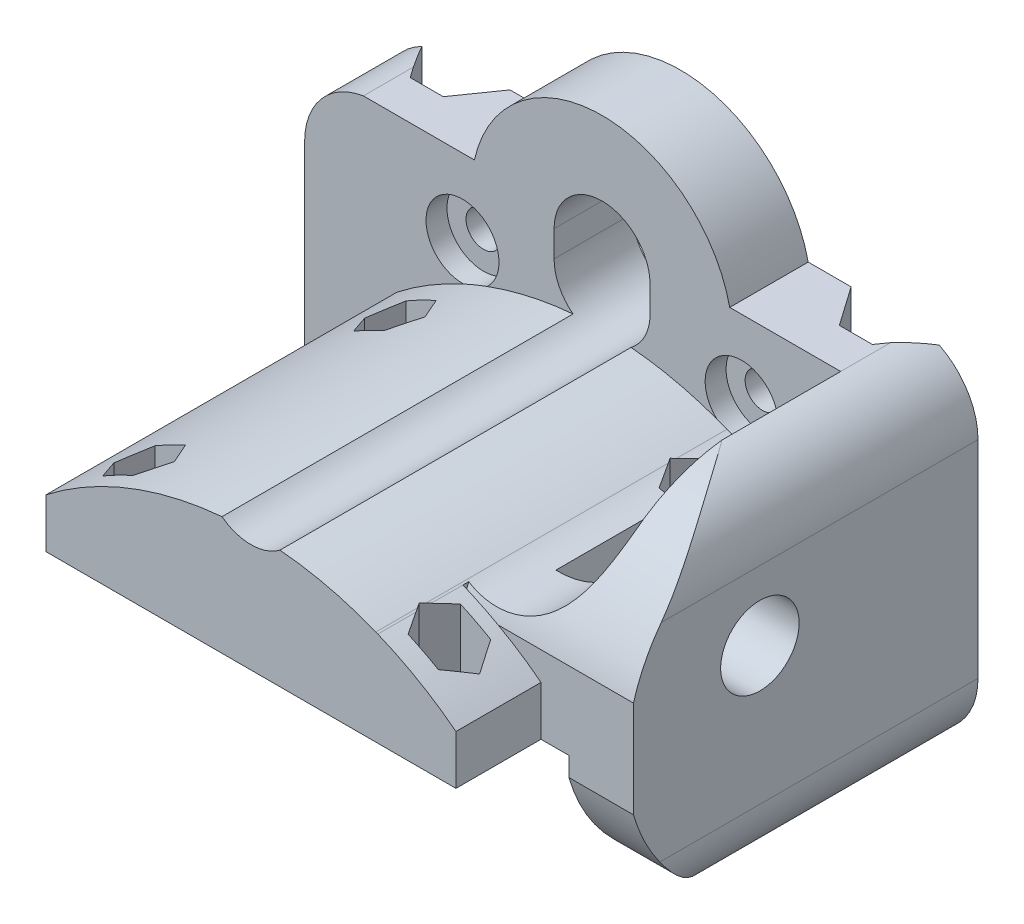
SolidWorks part; units mm, degrees
note: The reader was unsure of these and kept them because the rebuilt part matched: shared geometry of "Sketch9<7>".
ref_plane "Front Plane" through (0, 0, 0) normal (0, 0, 1) x (1, 0, 0)
ref_plane "Top Plane" through (0, 0, 0) normal (0, 1, 0) x (1, 0, 0)
ref_plane "Right Plane" through (0, 0, 0) normal (1, 0, 0) x (0, 0, -1)
sketch "Sketch1" plane through (0, 0, 0) normal (0, 0, 1) x (1, 0, 0)
  line L0 (34.1, -14.8502) -> (34.1, 8.8502)
  line L1 (-34.1, -14.8502) -> (-34.1, 8.8502)
  line L2 (-14.6356, 16.75) -> (-27.3591, 16.75)
  line L3 (14.6356, 16.75) -> (27.3591, 16.75)
  line L4 (-11.5, -22.75) -> (-27.5591, -22.75)
  line L5 (11.5, -22.75) -> (27.3591, -22.75)
  line L6 (7.5, -18.75) -> (7.5, -16.0002)
  line L7 (-7.5, -16.0002) -> (-7.5, -18.75)
  line L8 (0, -8.5446) -> (0, 28.5) construction
  line L9 (34.1, 0) -> (-34.1, 0) construction
  arc A0 (27.3591, -22.75) -> (34.1, -14.8502) centre (26.1005, -14.8502) ccw
  arc A1 (7.5, -18.75) -> (11.5, -22.75) centre (11.5, -18.75) ccw
  arc A2 (34.1, 8.8502) -> (27.3591, 16.75) centre (26.1005, 8.8502) ccw
  arc A3 (-34.1, 8.8502) -> (-27.3591, 16.75) centre (-26.1005, 8.8502) cw
  arc A4 (-27.3591, -22.75) -> (-34.1, -14.8502) centre (-26.1005, -14.8502) cw
  arc A5 (-7.5, -18.75) -> (-11.5, -22.75) centre (-11.5, -18.75) cw
  arc A6 (14.6356, 16.75) -> (-14.6356, 16.75) centre (0, 13.5101) ccw
  arc A7 (7.5, -16.0892) -> (-7.5, -16.0892) centre (0, -16.0447) ccw
  circle A8 centre (16.0001, 8) radius 2
  circle A9 centre (16.0001, -16.5) radius 2
  circle A10 centre (-16.0001, -16.5) radius 2
  circle A11 centre (-16.0001, 8) radius 2
  dimension "D1" = 4
  dimension "D2" = 4.0001
  dimension "D3" = 7.9995
  dimension "D4" = 4.0001
  dimension "D5" = 7.5
  dimension "D6" = 14.9899
  dimension "D7" = 7.5001
  dimension "D8" = 14.6356
  dimension "D9" = 16.0001
  dimension "D10" = 26.1005
  dimension "D11" = 27.3591
  dimension "D12" = 8
  dimension "D13" = 8.8502
  dimension "D14" = 14.8502
  dimension "D15" = 16.0002
  dimension "D18" = 27.5591
  dimension "D25" = 16.5
extrude "Boss-Extrude1" add sketch "Sketch1" along normal mid plane 9 contours A7 L6 A1 L5 A0 L0 A2 L3 A6 L2 A3 L1 A4 L4 A5 L7 A10 A9 A8 A11
sketch "Sketch3" plane through (0, 0, 4.5) normal (0, 0, 1) x (1, 0, 0)
  line L0 (0, 28.5) -> (0, -8.5446) construction
  line L1 (-5.5, 14.5) -> (-5.5, 11.5) construction
  line L6 (-5.5, 11.5) -> (-5.5, 14.5)
  line L7 (5.5, 11.5) -> (5.5, 14.5)
  line L14 (-34.1, -4.25) -> (34.1, -4.25) construction
  line L15 (-34.1, -14.8502) -> (-34.1, 8.8502) construction
  line L26 (34.1, -14.8502) -> (34.1, 8.8502) construction
  line L27 (11.5, -22.75) -> (27.3591, -22.75) construction
  arc A0 (14.6356, 16.75) -> (-14.6356, 16.75) centre (0, 13.5101) ccw construction
  circle A1 centre (-16.0001, 8) radius 4.1817
  arc A2 (7.5, -16.0892) -> (-7.5, -16.0892) centre (0, -16.0447) ccw construction
  arc A3 (-5.5, 14.5) -> (5.5, 14.5) centre (0, 14.5) cw
  arc A4 (-5.5, 11.5) -> (5.5, 11.5) centre (0, 11.5) ccw
  circle A5 centre (16.0001, 8) radius 4.1817
  circle A6 centre (16.0001, -16.5) radius 4.1817
  circle A7 centre (-16.0001, -16.5) radius 4.1817
  point P28 (0, 0)
  dimension "D1" = 32.8591
  dimension "D2" = 6.25
  dimension "D3" = 5.5
  dimension "D5" = 5.5
  dimension "D8" = 8.3635
  dimension "D4" = 14.5
  dimension "D6" = 3
  dimension "D7" = 5.5
  dimension "D10" = 37.25
sketch "Sketch4" plane through (0, 0, 4.5) normal (0, 0, 1) x (1, 0, 0)
  line L0 (5.5, 11.5) -> (5.5, 14.5) construction
  line L1 (-5.5, 11.5) -> (-5.5, 14.5) construction
  line L2 (5.5, 11.5) -> (5.5, 14.5)
  line L3 (-5.5, 11.5) -> (-5.5, 14.5)
  arc A0 (5.5, 14.5) -> (-5.5, 14.5) centre (0, 14.5) ccw construction
  arc A1 (-5.5, 11.5) -> (5.5, 11.5) centre (0, 11.5) ccw construction
  arc A2 (5.5, 14.5) -> (-5.5, 14.5) centre (0, 14.5) ccw
  arc A3 (-5.5, 11.5) -> (5.5, 11.5) centre (0, 11.5) ccw
extrude "Cut-Extrude2" cut sketch "Sketch4" against normal through all
sketch "Sketch6" plane through (0, 0, 4.5) normal (0, 0, 1) x (1, 0, 0)
  line L1 (23.5, -6.45) -> (-23.5, -6.45)
  line L2 (-23.5, -0.8) -> (23.5, -0.8)
  line L3 (-23.5, -0.8) -> (23.5, -0.8)
  line L4 (0, -8.5446) -> (0, -0.8) construction
  line L5 (-23.5, -0.8) -> (-23.5, -6.45)
  line L6 (-23.5, -6.45) -> (23.5, -6.45)
  line L7 (23.5, -0.8) -> (23.5, -6.45)
  arc A0 (3.324, 7.1181) -> (23.5, -0.8) centre (0, -31.0158) cw
  arc A2 (-5.5, 11.5) -> (5.5, 11.5) centre (0, 11.5) ccw construction
  arc A3 (-3.324, 7.1181) -> (3.324, 7.1181) centre (0, 11.5) ccw
  arc A4 (7.5, -16.0892) -> (-7.5, -16.0892) centre (0, -16.0447) ccw construction
  arc A6 (-23.5, -0.8) -> (-3.324, 7.1181) centre (0, -31.0158) cw
  point P4 (0, -6.45)
  arc M30 (5.5, 11.5) -> (-5.5, 11.5) centre (0, 11.5) cw
  dimension "D4" = 38.2785
  dimension "D1" = 47
  dimension "D2" = 0.8
  dimension "D3" = 5.65
extrude "Boss-Extrude2" add sketch "Sketch6" along normal blind 40.25 contours L4 L1 L7 L3 | L6 L4 L2 L5 | A6 L2 L3 A0 M30
sketch "Sketch9" plane through (0, 0, 0) normal (0, 1, 0) x (1, 0, 0)
  line L0 (-23.5, -44.75) -> (-3.324, -44.75) construction
  line L1 (-19.2321, -36.5) -> (-20.9641, -39.5)
  line L2 (-20.9641, -39.5) -> (-19.2321, -42.5)
  line L3 (-19.2321, -42.5) -> (-15.7679, -42.5)
  line L4 (-15.7679, -42.5) -> (-14.0359, -39.5)
  line L5 (-14.0359, -39.5) -> (-15.7679, -36.5)
  line L6 (-15.7679, -36.5) -> (-19.2321, -36.5)
  line L9 (0, 4.5) -> (0, -44.75) construction
  line L10 (14.6356, 4.5) -> (-14.6356, 4.5) construction
  line L11 (-3.324, -44.75) -> (3.324, -44.75) construction
  line L12 (14.0359, -39.5) -> (15.7679, -36.5)
  line L13 (15.7679, -42.5) -> (14.0359, -39.5)
  line L14 (19.2321, -42.5) -> (15.7679, -42.5)
  line L15 (20.9641, -39.5) -> (19.2321, -42.5)
  line L16 (19.2321, -36.5) -> (20.9641, -39.5)
  line L17 (15.7679, -36.5) -> (19.2321, -36.5)
  line L18 (22.7061, 0) -> (19.5551, 4.5)
  line L19 (-29.647, 4.5) -> (-26.4961, 0)
  line L20 (26.4961, 0) -> (22.7061, 0)
  line L21 (-26.4961, 0) -> (-22.7061, 0)
  line L22 (-22.7061, 0) -> (-19.5551, 4.5)
  line L23 (29.647, 4.5) -> (26.4961, 0)
  line L24 (19.5551, 4.5) -> (29.647, 4.5)
  line L25 (-23.5, -25.1222) -> (23.5, -25.1222) construction
  line L26 (23.5, -44.75) -> (23.5, -4.5) construction
  line L27 (14.0359, -10.7444) -> (15.7679, -13.7444)
  line L28 (15.7679, -7.7444) -> (14.0359, -10.7444)
  line L29 (19.2321, -7.7444) -> (15.7679, -7.7444)
  line L30 (20.9641, -10.7444) -> (19.2321, -7.7444)
  line L31 (-23.5, -44.75) -> (-23.5, -4.5) construction
  line L32 (19.2321, -13.7444) -> (20.9641, -10.7444)
  line L34 (15.7679, -13.7444) -> (19.2321, -13.7444)
  line L35 (-14.0359, -10.7444) -> (-15.7679, -13.7444)
  line L36 (-27.3591, 4.5) -> (-34.1, 4.5) construction
  line L38 (-19.5551, 4.5) -> (-29.647, 4.5)
  line L39 (-15.7679, -7.7444) -> (-14.0359, -10.7444)
  line L40 (-19.2321, -7.7444) -> (-15.7679, -7.7444)
  line L41 (-20.9641, -10.7444) -> (-19.2321, -7.7444)
  line L42 (-19.2321, -13.7444) -> (-20.9641, -10.7444)
  line L43 (-15.7679, -13.7444) -> (-19.2321, -13.7444)
  circle A0 centre (17.5, -10.7444) radius 1.8
  circle A1 centre (-17.5, -39.5) radius 3 construction
  circle A2 centre (-17.5, -39.5) radius 1.8
  circle A3 centre (17.5, -39.5) radius 1.8
  circle A4 centre (-17.5, -10.7444) radius 1.8
  point P38 (17.5, -10.7444)
  point P53 (-17.5, -10.7444)
  dimension "D4" = 6
  dimension "D5" = 125
  dimension "D7" = 3.6
  dimension "D1" = 125
  dimension "D2" = 6
  dimension "D3" = 5.25
  dimension "D6" = 4.453
  dimension "D8" = 3.79
  dimension "D9" = 14.3778
sketch "Sketch10" plane through (0, 0, 0) normal (1, 0, 0) x (0, 0, -1)
  circle A0 centre (-3.55, -1.87) radius 1.25
  circle A1 centre (-3.55, -11.33) radius 1.25
  point P0 (0, 0)
  dimension "D1" = 2.5
  dimension "D2" = 2.5
  dimension "D3" = 3.55
  dimension "D4" = 1.87
  dimension "D5" = 11.33
extrude "Cut-Extrude3" cut sketch "Sketch3" against normal blind 2.4
ref_plane "Plane1" through (-34.1, 0, 0) normal (-1, 0, 0) x (0, 0, 1)
ref_plane "Plane2" through (0, 0, 4.5) normal (0, 0, 1) x (1, 0, 0)
sketch "Sketch15" plane through (0, 0, 4.5) normal (0, 0, 1) x (1, 0, 0)
  line L0 (14.3143, 16.75) -> (14.3143, -22.75)
  line L1 (14.6356, 16.75) -> (27.3591, 16.75) construction
  line L2 (11.5, -22.75) -> (27.3591, -22.75) construction
  line L3 (34.1, -14.8502) -> (34.1, 8.8502) construction
  line L4 (34.1, -14.8502) -> (34.1, 8.8502)
  line L5 (14.3143, -22.75) -> (27.3591, -22.75)
  line L6 (14.3143, 16.75) -> (27.3591, 16.75)
  arc A0 (34.1, 8.8502) -> (27.3591, 16.75) centre (26.1005, 8.8502) ccw construction
  arc A1 (27.3591, -22.75) -> (34.1, -14.8502) centre (26.1005, -14.8502) ccw construction
  arc A2 (34.1, 8.8502) -> (27.3591, 16.75) centre (26.1005, 8.8502) ccw
  arc A3 (27.3591, -22.75) -> (34.1, -14.8502) centre (26.1005, -14.8502) ccw
  dimension "D1" = 19.7857
extrude "Boss-Extrude3" add sketch "Sketch15" along normal blind 30.5
sketch "Sketch17" plane through (0, 0, 0) normal (1, 0, 0) x (0, 0, -1)
  line L0 (-35, -8.6461) -> (-35, 2.4461)
  line L1 (-38.1156, 25) -> (-38.1156, -25)
  line L2 (0, 0) -> (-38.1156, 0) construction
  line L8 (-18.1156, 16.75) -> (-18.1156, 25)
  line L12 (-18.1156, 25) -> (-38.1156, 25)
  line L15 (-38.1156, -25) -> (-19.4504, -25)
  line L16 (-19.4504, -25) -> (-19.4504, -22.75)
  arc A0 (-19.4504, -22.75) -> (-35, -8.6461) centre (-15.8631, -3.1713) cw
  arc A1 (-35, 2.4461) -> (-18.1156, 16.75) centre (-15.8232, -3.0731) cw
  point P8 (0, 0)
  dimension "D1" = 19.9046
  dimension "D2" = 19.9552
  dimension "D3" = 50
  dimension "D4" = 15.8232
  dimension "D5" = 15.8631
  dimension "D6" = 18.1156
  dimension "D7" = 19.4504
  dimension "D8" = 35
  dimension "D9" = 2.4461
  dimension "D10" = 3.1713
  dimension "D11" = 20
sketch "Sketch18" plane through (0, 0, 0) normal (0, 0, 1) x (1, 0, 0)
  line L0 (26.6868, 12.5458) -> (26.6868, 18.5458)
  line L1 (26.7, -25.0473) -> (26.7, -6.35)
  line L3 (23.5, -6.45) -> (-23.5, -6.45) construction
  line L4 (26.7, -6.45) -> (14.3143, -6.45)
  line L10 (13.9387, 4.6347) -> (13.9387, 18.5458)
  line L11 (13.9387, 18.5458) -> (26.6868, 18.5458)
  line L12 (14.3143, -6.45) -> (14.3143, -25.0473)
  line L13 (14.3143, -25.0473) -> (14.2319, -25.0492)
  line L14 (26.7, -25.0473) -> (14.3143, -25.0473)
  arc A0 (26.6868, 12.5458) -> (13.9387, 4.6347) centre (17.3234, 13.4072) cw
  arc A1 (23.5, -0.8) -> (3.324, 7.1181) centre (0, -31.0158) ccw construction
  point P2 (0, 0)
  dimension "D1" = 9.4029
  dimension "D2" = 13.9387
  dimension "D3" = 14.2319
  dimension "D4" = 14.3143
  dimension "D5" = 17.3234
  dimension "D6" = 26.6868
  dimension "D7" = 26.7
  dimension "D8" = 18.5458
  dimension "D9" = 6.35
  dimension "D10" = 25.0473
  dimension "D11" = 25.0492
ref_plane "Plane3" through (0, 0, 4.5) normal (0, 0, 1) x (1, 0, 0)
ref_plane "Plane4" through (34.1, 0, 0) normal (1, 0, 0) x (0, 0, -1)
sketch "Sketch21" plane through (0, 0, 4.5) normal (0, 0, 1) x (1, 0, 0)
  line L0 (14.3143, -25.0473) -> (14.2319, -25.0492) construction
  line L1 (26.7, -6.45) -> (14.3143, -6.45) construction
  line L2 (14.3143, -6.45) -> (14.3143, -25.0473) construction
  line L3 (26.7, -25.0473) -> (26.7, -6.35) construction
  line L4 (26.7, -25.0473) -> (14.3143, -25.0473) construction
  line L5 (14.3143, 16.75) -> (27.3591, 16.75)
  line L8 (14.3143, -25.0473) -> (14.2319, -25.0492)
  line L9 (26.7, -6.45) -> (14.3143, -6.45)
  line L10 (14.3143, -6.45) -> (14.3143, -25.0473)
  line L11 (26.7, -25.0473) -> (26.7, -6.35)
  line L12 (26.7, -25.0473) -> (14.3143, -25.0473)
  line L13 (27.3591, 12.5796) -> (27.3591, 16.75)
  line L15 (14.3143, 16.75) -> (14.3143, 4.4855) construction
  line L16 (27.3591, 16.75) -> (14.3143, 16.75) construction
  line L17 (14.3143, 16.75) -> (14.3143, 4.4855)
  line L18 (27.3591, 16.75) -> (14.3143, 16.75)
  arc A1 (27.3591, 12.5796) -> (14.3143, 4.4855) centre (17.9734, 13.1473) cw
  point P8 (0, 0)
  point P11 (27.3591, 16.75)
  dimension "D1" = 9.4029
  dimension "D3" = 17.9734
  dimension "D4" = 16.75
extrude "Cut-Extrude16" cut sketch "Sketch21" along normal through all contours L12 L11 L9 L10 | A1 L13 L5 L17
sketch "Sketch22" plane through (34.1, 0, 0) normal (1, 0, 0) x (0, 0, -1)
  line L0 (-35, 2.4461) -> (-35, 18.4461)
  line L1 (-35, 16.75) -> (-4.5, 16.75) construction
  line L2 (-19.4504, -22.75) -> (-19.4504, -24.6461)
  line L3 (-35, -24.6461) -> (-35, -8.6461)
  line L4 (-19.4504, -24.6461) -> (-35, -24.6461)
  line L6 (-38.1156, -25) -> (-19.4504, -25)
  line L7 (-38.1156, 25) -> (-38.1156, -25)
  line L8 (-18.1156, 25) -> (-38.1156, 25)
  line L9 (-18.1156, 16.75) -> (-18.1156, 25)
  line L10 (-35, -8.6461) -> (-35, 2.4461)
  line L11 (-19.4504, -25) -> (-19.4504, -22.75)
  line L20 (-18.1154, 16.75) -> (-18.1154, 18.4461)
  line L21 (-18.1154, 18.4461) -> (-35, 18.4461)
  arc A2 (-18.1156, 16.75) -> (-35, 2.4461) centre (-15.8232, -3.0731) ccw
  arc A3 (-35, -8.6461) -> (-19.4504, -22.75) centre (-15.8631, -3.1713) ccw
  arc A4 (-18.1154, 16.75) -> (-35, 2.4461) centre (-15.8232, -3.0731) ccw
  arc A5 (-35, -8.6461) -> (-19.4504, -22.75) centre (-15.8631, -3.1713) ccw
  dimension "D2" = 16
  dimension "D3" = 16
  dimension "D1" = 0
extrude "Cut-Extrude20" cut sketch "Sketch22" against normal up to vertex (19.5559 mm away)
sketch "Sketch24" plane through (0, 0, 0) normal (0, 1, 0) x (1, 0, 0)
  line L0 (17.75, -16.1355) -> (19.6355, -14.25)
  line L1 (19.6355, -14.25) -> (26.7, -14.25)
  line L2 (26.7, -14.25) -> (26.7, -27.55)
  line L3 (26.7, -27.55) -> (17.75, -27.55)
  line L4 (17.75, -27.55) -> (17.75, -16.1355)
  point P2 (0, 0)
  dimension "D1" = 17.75
  dimension "D2" = 19.6355
  dimension "D3" = 26.7
  dimension "D4" = 14.25
  dimension "D5" = 16.1355
  dimension "D6" = 27.55
extrude "Cut-Extrude21" cut sketch "Sketch24" against normal through all both and the other way through all
extrude "Cut-Extrude6" cut sketch "Sketch9<7>" along normal through all and the other way offset from surface (4.1004 mm away) 2.3496 contours L5 L6 L1 L2 L3 L4 A2 | L17 L12 L13 L14 L15 L16 A3 | L27 L34 L32 L30 L29 L28 A0 | L43 L35 L39 L40 L41 L42 A4 other way up to face at (14.7214, -6.45, 24.385)
sketch "Sketch9<7>" plane through (0, 0, 0) normal (0, 1, 0) x (1, 0, 0) same geometry as "Sketch9"
extrude "Cut-Extrude5" cut sketch "Sketch9" against normal through all both and the other way through all contours A2 | A3 | A4 | L22 L38 L19 L21 | L24 L18 L20 L23 | A0
sketch "Sketch31" plane through (0, 0, 0) normal (1, 0, 0) x (0, 0, -1)
  circle A0 centre (-20.5054, 0.9021) radius 4.4969
  point P0 (0, 0)
  dimension "D1" = 8.9938
  dimension "D2" = 20.5054
  dimension "D3" = 0.9021
sketch "Sketch32" plane through (34.1, 0, 0) normal (1, 0, 0) x (0, 0, -1)
  line L4 (-31.9814, -14.8502) -> (4.5, -14.8502)
  line L5 (4.5, -14.8502) -> (4.5, 8.8502)
  line L6 (4.5, 8.8502) -> (-31.8247, 8.8502)
  line L7 (-35, 2.4461) -> (-35, -8.6461)
  line L8 (-31.9814, -14.8502) -> (4.5, -14.8502)
  line L9 (4.5, -14.8502) -> (4.5, 8.8502)
  line L10 (4.5, 8.8502) -> (-31.8247, 8.8502)
  line L11 (-35, 2.4461) -> (-35, -8.6461)
  circle A1 centre (-20.5054, 0.9021) radius 4.4969
  arc A2 (-35, -8.6461) -> (-31.9814, -14.8502) centre (-15.8631, -3.1713) ccw
  arc A3 (-31.8247, 8.8502) -> (-35, 2.4461) centre (-15.8232, -3.0731) ccw
  arc A4 (-35, -8.6461) -> (-31.9814, -14.8502) centre (-15.8631, -3.1713) ccw
  arc A5 (-31.8247, 8.8502) -> (-35, 2.4461) centre (-15.8232, -3.0731) ccw
  circle A6 centre (-20.5054, 0.9021) radius 4.4969
  dimension "D1" = 0
  dimension "D2" = 0
extrude "Cut-Extrude28" cut sketch "Sketch32" against normal up to surface (7.4 mm away) contours A6 up to face at (26.7, -8.5621, 20.3511)
